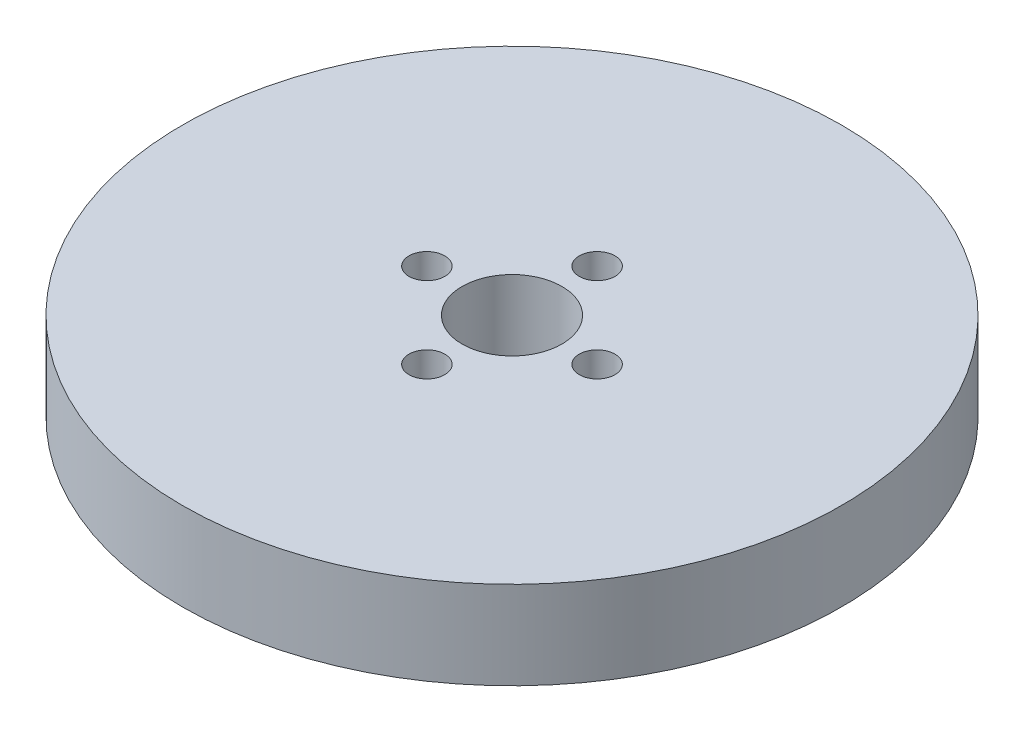
SolidWorks part; units mm, degrees
ref_plane "Front Plane" through (0, 0, 0) normal (0, 0, 1) x (1, 0, 0)
ref_plane "Top Plane" through (0, 0, 0) normal (0, 1, 0) x (1, 0, 0)
ref_plane "Right Plane" through (0, 0, 0) normal (1, 0, 0) x (0, 0, -1)
sketch "Sketch1" plane through (0, 0, 0) normal (0, 1, 0) x (1, 0, 0)
  circle A0 centre (0, 0) radius 82.5
  dimension "FLANGE_OD" = 165
extrude "Boss-Extrude1" add sketch "Sketch1" along normal blind 22
sketch "Sketch2" plane through (0, 0, 0) normal (0, 1, 0) x (1, 0, 0)
  circle A0 centre (0, 0) radius 12.5
  dimension "BORE_D" = 25
extrude "Cut-Extrude1" cut sketch "Sketch2" along normal through all
sketch "Sketch3" plane through (0, 22, 0) normal (0, 1, 0) x (1, 0, 0)
  circle A0 centre (0, 0) radius 21.3071 construction
  circle A1 centre (-21.3071, 0) radius 4.4732
  dimension "BOLT_D" = 8.9464
  dimension "BOLT_PCD" = 42.6142
extrude "Cut-Extrude2" cut sketch "Sketch3" against normal blind 13.7994
pattern_circular "CirPattern1" count 4 over 360 about axis through (0, 0, 0) along (0, 1, 0) of "Cut-Extrude2"
